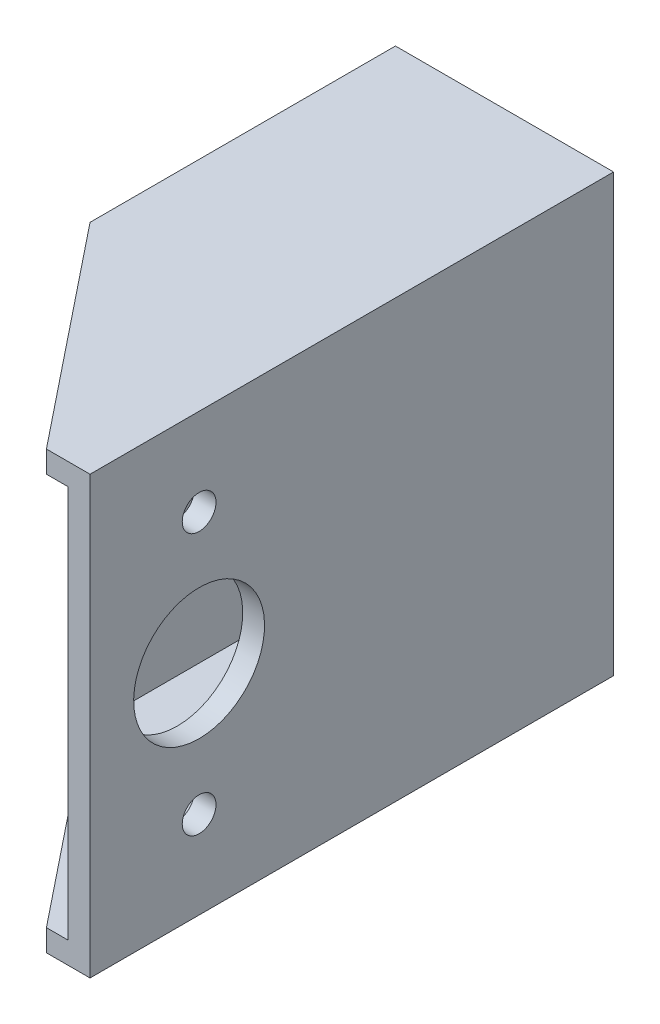
SolidWorks part; units mm, degrees
ref_plane "Front Plane" through (0, 0, 0) normal (0, 0, 1) x (1, 0, 0)
ref_plane "Top Plane" through (0, 0, 0) normal (0, 1, 0) x (1, 0, 0)
ref_plane "Right Plane" through (0, 0, 0) normal (1, 0, 0) x (0, 0, -1)
sketch "Sketch1" plane through (0, 0, 0) normal (0, 0, 1) x (1, 0, 0)
  line L1 (-12.1647, 2.5103) -> (19.5853, 2.5103)
  line L2 (-12.1647, 2.5103) -> (-12.1647, -60.9897)
  line L3 (-12.1647, -60.9897) -> (19.5853, -60.9897)
  line L4 (19.5853, 2.5103) -> (19.5853, -60.9897)
  line L5 (-8.9897, -0.6647) -> (16.4103, -0.6647)
  line L6 (-8.9897, -0.6647) -> (-8.9897, -57.8147)
  line L7 (-8.9897, -57.8147) -> (16.4103, -57.8147)
  line L8 (16.4103, -0.6647) -> (16.4103, -57.8147)
  dimension "D1" = 63.5
  dimension "D2" = 31.75
  dimension "D3" = 3.175
  dimension "D4" = 3.175
  dimension "D5" = 3.175
  dimension "D6" = 3.175
extrude "Boss-Extrude1" add sketch "Sketch1" along normal blind 76.2
sketch "Sketch2" plane through (0, 2.5103, 0) normal (0, 1, 0) x (1, 0, 0)
  line L0 (13.2353, -76.2) -> (-12.1647, -44.45)
  line L1 (19.5853, -76.2) -> (-12.1647, -76.2) construction
  line L2 (-12.1647, -76.2) -> (-12.1647, 0) construction
  line L3 (-12.1647, -44.45) -> (-12.1647, -76.2)
  line L4 (-12.1647, -76.2) -> (13.2353, -76.2)
  line L5 (13.2353, -76.2) -> (13.5724, -152.4399)
  line M4 (-12.1647, 0) -> (-12.1647, -76.2)
  line M5 (-12.1647, -76.2) -> (19.5853, -76.2)
  dimension "D1" = 31.75
  dimension "D2" = 25.4
extrude "Cut-Extrude1" cut sketch "Sketch2" against normal up to surface (63.5 mm away) contours L0 M5 M4 region at (-3.6981, 2.5103, 65.6167) up to face at (3.7103, -60.9897, 38.1)
sketch "Sketch3" plane through (16.4103, 0, 0) normal (-1, 0, 0) x (0, 0, 1)
  line L0 (76.2, -57.8147) -> (76.2, -0.6647) construction
  line L1 (44.45, -60.9897) -> (76.2, -60.9897) construction
  line L2 (76.2, -29.2397) -> (48.4187, -29.2397)
  line L3 (48.4187, -57.8147) -> (48.4187, -0.6647) construction
  circle A0 centre (60.325, -29.2397) radius 9.525
  point P0 (60.325, -48.2897)
  point P9 (60.325, -10.1897)
  point P12 (0, 0)
  dimension "D3" = 15.875
  dimension "D4" = 19.05
  dimension "D1" = 15.875
  dimension "D2" = 12.7
extrude "Cut-Extrude2" cut sketch "Sketch3" against normal up to surface (3.175 mm away) contours A0 up to face at (19.5853, -29.2397, 38.1)
hole_wizard "#10 (0.1935) Diameter Hole1" positions "3DSketch1" profile "Sketch4" hole size "#10" standard "ANSI Inch" end condition through all
sketch3d "3DSketch1"
  point P0 (16.4103, -48.2897, 60.325)
  point P3 (16.4103, -10.1897, 60.325)
sketch "Sketch4" plane through (16.4103, -48.2897, 60.325) normal (0, 1, 0) x (0, 0, 1)
  line L0 (0, 0) -> (0, 3.175)
  line L1 (0, 3.175) -> (2.4574, 3.175)
  line L2 (2.4574, 3.175) -> (2.4574, 0)
  line L5 (2.4574, 0) -> (0, 0)
  line L11 (0, -6.35) -> (0, 107.95) construction
  dimension "Thru Hole Dia." = 4.9149
  dimension "Thru Hole Depth" = 3.175
